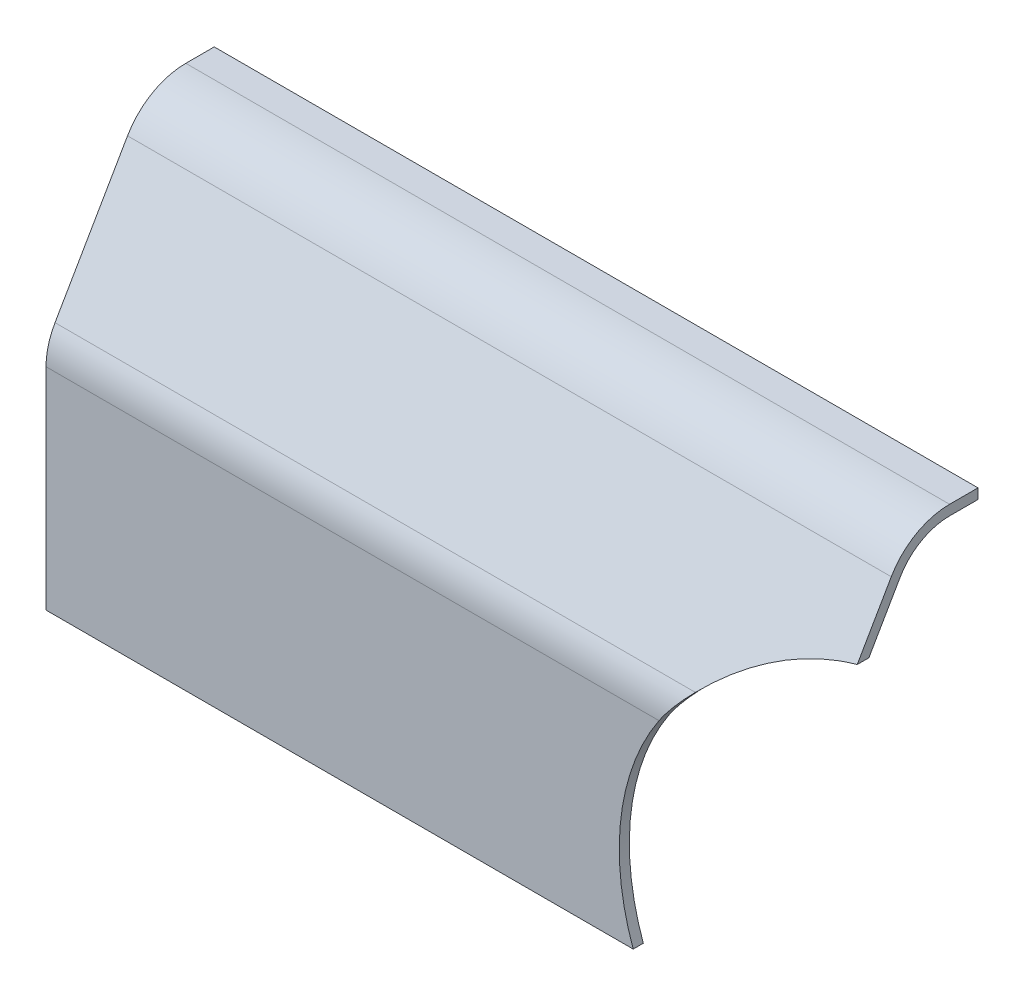
SolidWorks part; units mm, degrees
ref_plane "Alzado" through (0, 0, 0) normal (0, 0, 1) x (1, 0, 0)
ref_plane "Planta" through (0, 0, 0) normal (0, 1, 0) x (1, 0, 0)
ref_plane "Vista lateral" through (0, 0, 0) normal (1, 0, 0) x (0, 0, -1)
sketch "Croquis1" plane through (0, 0, 0) normal (1, 0, 0) x (0, 0, -1)
  line L0 (0, 0) -> (0, 67.1962)
  line L1 (0, 67.1962) -> (28.7321, 116.9615)
  line L2 (28.7321, 116.9615) -> (47, 116.9615)
  line L3 (47, 116.9615) -> (47, 119.9615)
  line L4 (47, 119.9615) -> (27, 119.9615)
  line L5 (27, 119.9615) -> (-3, 68)
  line L6 (-3, 68) -> (-3, 0)
  line L7 (-3, 0) -> (0, 0)
  line L8 (0, 67.1962) -> (29.2398, 67.1962) construction
  dimension "D1" = 3
  dimension "D2" = 3
  dimension "D3" = 3
  dimension "D4" = 68
  dimension "D5" = 60
  dimension "D6" = 20
  dimension "D7" = 60
extrude "Saliente-Extruir1" add sketch "Croquis1" along normal mid plane 227
fillet "Redondeo1" radius 20 1 edges at (0, 68, 3)
fillet "Redondeo2" radius 20 1 edges at (0, 119.9615, -27)
fillet "Redondeo3" radius 17 1 edges at (0, 116.9615, -28.7321)
fillet "Redondeo4" radius 17 1 edges at (0, 67.1962, 0)
sketch "Croquis2" plane through (0, 0, 3) normal (0, 0, 1) x (1, 0, 0)
  circle A0 centre (126.88, 23.7215) radius 70
  dimension "D1" = 140
  dimension "D2" = 13.38
  dimension "D3" = 86.24
extrude "Cortar-Extruir1" cut sketch "Croquis2" against normal through all
